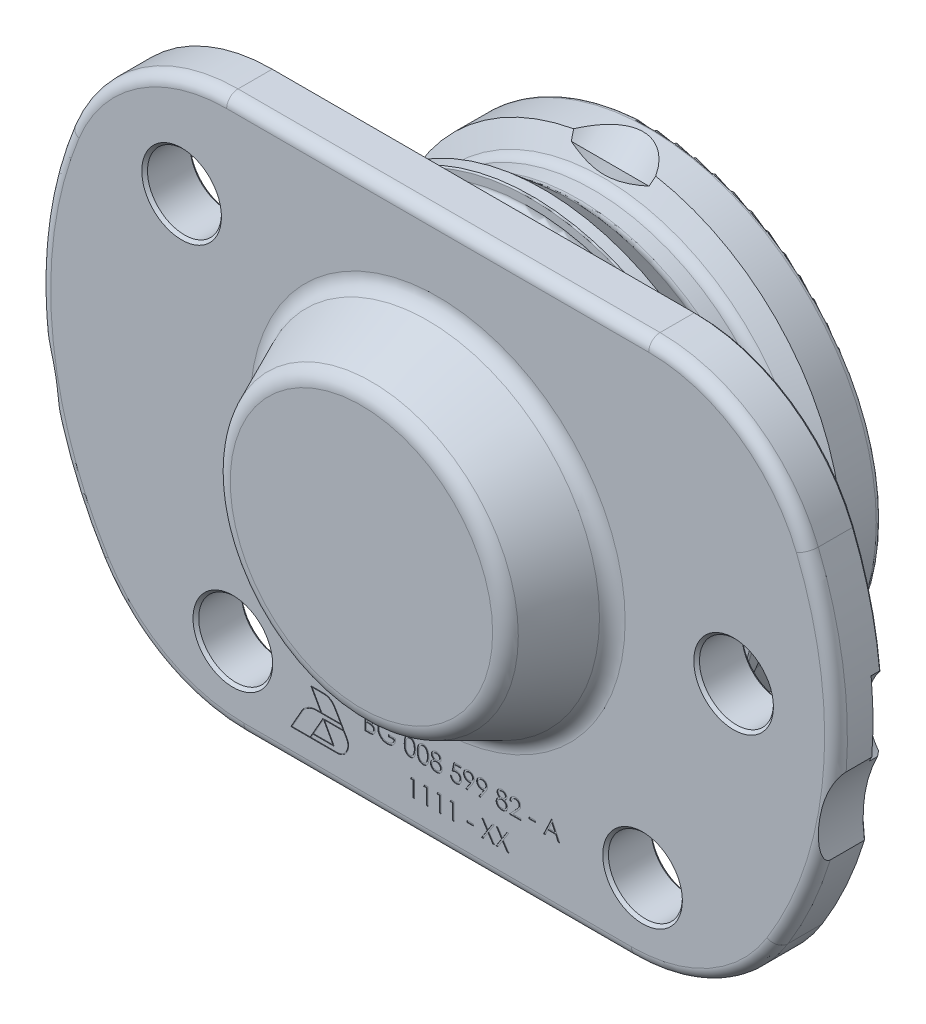
SolidWorks part; units mm, degrees
material "4140 H/T"
ref_plane "Front Plane" through (0, 0, 0) normal (0, 0, 1) x (1, 0, 0)
ref_plane "Top Plane" through (0, 0, 0) normal (0, 1, 0) x (1, 0, 0)
ref_plane "Right Plane" through (0, 0, 0) normal (1, 0, 0) x (0, 0, -1)
sketch "Sketch1" plane through (0, 0, 0) normal (0, 0, 1) x (1, 0, 0)
  line L0 (0, 0) -> (0, 80.5895) construction
  line L1 (0, 0) -> (-118.5076, 0) construction
  line L2 (0, 0) -> (36, -37.5233) construction
  line L3 (37.081, 45) -> (-37.081, 45)
  line L4 (-34.0441, -51) -> (34.0441, -51)
  circle A0 centre (52, 0) radius 6.5
  circle A1 centre (36, -37.5233) radius 6.5
  circle A2 centre (-36, -37.5233) radius 6.5
  circle A3 centre (-45, 26.0576) radius 6.5
  arc A4 (-37.081, 45) -> (-64.8917, 26.25) centre (-37.081, 15) ccw
  arc A5 (-64.8917, 26.25) -> (-59.5772, -36.75) centre (0, 0) ccw
  arc A6 (-59.5772, -36.75) -> (-34.0441, -51) centre (-34.0441, -21) ccw
  arc A7 (59.5772, -36.75) -> (34.0441, -51) centre (34.0441, -21) cw
  arc A8 (64.8917, 26.25) -> (59.5772, -36.75) centre (0, 0) cw
  arc A9 (37.081, 45) -> (64.8917, 26.25) centre (37.081, 15) cw
  circle A10 centre (0, 0) radius 52 construction
  point P26 (0, -51)
  point P32 (0, 45)
  dimension "D1" = 13
  dimension "D5" = 30
  dimension "D6" = 30
  dimension "D7" = 140
  dimension "D8" = 70
  dimension "D9" = 104
  dimension "D10" = 45
  dimension "D11" = 36
  dimension "D12" = 36
  dimension "D2" = 45
  dimension "D3" = 51
  dimension "D13" = 46.187
extrude "Extrude1" add sketch "Sketch1" along normal blind 8.5
sketch "Sketch2" plane through (0, 0, 0) normal (1, 0, 0) x (0, 0, -1)
  line L0 (0, 0) -> (34.8512, 0) construction
  line L1 (0, 39.975) -> (3.85, 39.975)
  line L2 (0, 26.25) -> (0, 45) construction
  line L3 (4.1, 39.725) -> (4.1, 38.35)
  line L4 (4.9, 37.55) -> (7, 37.55)
  line L5 (7.8, 38.35) -> (7.8, 39.725)
  line L6 (8.05, 39.975) -> (10.1, 39.975)
  line L7 (109.361, 150.8299) -> (109.361, 125.8299) construction
  line L8 (29.6, 38.975) -> (29.6, 0)
  line L9 (0, 39.975) -> (-8.5, 39.975)
  line L10 (-8.5, 45) -> (-8.5, 26.25) construction
  line L11 (-8.5, 39.975) -> (-8.5, 32.9437)
  line L12 (-8.5, 26.25) -> (-8.5, -36.75) construction
  line L13 (-10.274, 30.2057) -> (-20.126, 25.7943)
  line L14 (-21.9, 23.0563) -> (-21.9, 0)
  line L15 (29.6, 0) -> (-21.9, 0)
  line L16 (10.1, 39.975) -> (14.8755, 35.9679)
  line L17 (22.6, 39.975) -> (20.5937, 36.5)
  line L18 (18.8617, 35.5) -> (16.161, 35.5)
  line L19 (22.6, 39.975) -> (28.6, 39.975)
  line L20 (62.484, 84.927) -> (62.484, 164.927) construction
  line L21 (60.9185, 95.9953) -> (60.9185, 65.5229) construction
  line L22 (57.8623, 92.6695) -> (57.8623, 65.5229) construction
  line L23 (79.7053, 87.2761) -> (79.7053, 68.4893) construction
  line L24 (64.6938, 84.6693) -> (67.4146, 89.3819) construction
  line L25 (67.4146, 89.3819) -> (71.4823, 89.3819) construction
  line L26 (71.4823, 89.3819) -> (77.0985, 84.6693) construction
  line L27 (64.6938, 84.6693) -> (38.8957, 84.6693) construction
  line L28 (88.1305, 125.8299) -> (6.95, 125.8299) construction
  line L29 (74.2904, 87.0256) -> (85.5084, 101.1776) construction
  line L30 (109.361, 125.8299) -> (96.5029, 125.8299) construction
  line L31 (96.5029, 125.8299) -> (96.5029, 156.8299) construction
  line L32 (87.7036, 81.3976) -> (95.948, 81.3976) construction
  line L33 (109.361, 133.7274) -> (57.8623, 133.7274) construction
  line L34 (87.7036, 81.3976) -> (87.7036, 62.5034) construction
  arc A0 (-20.126, 25.7943) -> (-21.9, 23.0563) centre (-18.9, 23.0563) ccw
  arc A1 (-8.5, 32.9437) -> (-10.274, 30.2057) centre (-11.5, 32.9437) cw
  arc A2 (4.1, 38.35) -> (4.9, 37.55) centre (4.9, 38.35) ccw
  arc A3 (7, 37.55) -> (7.8, 38.35) centre (7, 38.35) ccw
  arc A4 (7.8, 39.725) -> (8.05, 39.975) centre (8.05, 39.725) cw
  arc A5 (3.85, 39.975) -> (4.1, 39.725) centre (3.85, 39.725) cw
  arc A6 (20.5937, 36.5) -> (18.8617, 35.5) centre (18.8617, 37.5) cw
  arc A7 (14.8755, 35.9679) -> (16.161, 35.5) centre (16.161, 37.5) ccw
  arc A8 (29.6, 38.975) -> (28.6, 39.975) centre (28.6, 38.975) ccw
  point P23 (-21.9, 25)
  point P26 (-8.5, 31)
  dimension "D4" = 3
  dimension "D12" = 0.8
  dimension "D13" = 0.25
  dimension "D29" = 2
  dimension "D10" = 1
  dimension "D2" = 50
  dimension "D3" = 62
  dimension "D5" = 79.95
  dimension "D6" = 29.6
  dimension "D7" = 75.1
  dimension "D8" = 3.7
  dimension "D9" = 21.8
  dimension "D11" = 2.425
  dimension "D14" = 51.5
  dimension "D15" = 80
  dimension "D16" = 6.8316
  dimension "D17" = 19.2363
  dimension "D18" = 60
  dimension "D19" = 40
  dimension "D20" = 21.8431
  dimension "D21" = 19.2363
  dimension "D22" = 7
  dimension "D23" = 19.5
  dimension "D24" = 60
  dimension "D25" = 40
  dimension "D26" = 71
  dimension "D27" = 3.0562
  dimension "D28" = 51.597
  dimension "D30" = 25
  dimension "D31" = 31
  dimension "D32" = 51.4987
revolve "Revolve1" add sketch "Sketch2" angle 360 about L0
fillet "Fillet5" radius 0.8 1 edges at (39.975, 0, 0)
sketch "Sketch3" plane through (0, 0, 0) normal (1, 0, 0) x (0, 0, -1)
  line L0 (0, 0) -> (47.3873, 0) construction
  line L1 (29.6, 32) -> (26.8929, 29.2929)
  line L3 (26.1858, 29) -> (-1.3282, 29)
  line L4 (-3.3282, 28.4641) -> (-12.4, 23.2265)
  line L5 (-14.4, 19.7624) -> (-14.4, 0)
  line L6 (29.6, 32) -> (29.6, 0)
  line L7 (-14.4, 0) -> (29.6, 0)
  line L9 (29.6, 38.975) -> (29.6, 0) construction
  arc A0 (-12.4, 23.2265) -> (-14.4, 19.7624) centre (-10.4, 19.7624) ccw
  arc A1 (-1.3282, 29) -> (-3.3282, 28.4641) centre (-1.3282, 25) ccw
  arc A2 (26.8929, 29.2929) -> (26.1858, 29) centre (26.1858, 30) cw
  point P13 (-14.4, 22.0718)
  point P16 (-2.4, 29)
  point P19 (26.6, 29)
  dimension "D7" = 4
  dimension "D8" = 1
  dimension "D1" = 64
  dimension "D2" = 58
  dimension "D3" = 45
  dimension "D4" = 32
  dimension "D5" = 44
  dimension "D6" = 30
  dimension "D9" = 3
revolve "Cut-Revolve1" cut sketch "Sketch3" angle 360 about L0
ref_plane "Plane3" through (0, 0, -20.6) normal (0, 0, -1) x (-1, 0, 0)
fillet "Fillet1" radius 2 8 edges at (53.8515, 39.8747, 8.5) (69.7522, -5.8842, 8.5) (48.6643, -47.1964, 8.5) (0, -51, 8.5) (-48.6643, -47.1964, 8.5) (-69.7522, -5.8842, 8.5) (-53.8515, 39.8747, 8.5) (0, 45, 8.5)
sketch "Sketch9" plane through (0, 0, 0) normal (1, 0, 0) x (0, 0, -1)
  line L0 (22.8839, -48.7703) -> (-1.0551, -20.241) construction
  line L1 (13.6, -37.7062) -> (15.5151, -36.0993) construction
  line L2 (15.5151, -36.0993) -> (12.3012, -32.2691)
  line L3 (13.6, -37.7062) -> (2.8578, -24.9042)
  line L4 (29.7, -38.975) -> (29.7, 38.975) construction
  line L5 (0, 0) -> (43.186, 0) construction
  line L6 (2.8578, -24.9042) -> (3.6239, -24.2615)
  line L7 (7.6, -29) -> (7.6, -24.6889) construction
  line L8 (12.3012, -32.2691) -> (10.5728, -32.5428)
  line L9 (10.5728, -32.5428) -> (3.6239, -24.2615)
  line L10 (29.6, -32) -> (29.6, 32) construction
  line L11 (15.5151, -36.0993) -> (20.5701, -42.1235)
  line L12 (20.5701, -42.1235) -> (18.6549, -43.7305)
  line L13 (13.6, -37.7062) -> (18.6549, -43.7305)
  dimension "D1" = 5
  dimension "D2" = 14.1849
  dimension "D3" = 37.7062
  dimension "D4" = 29
  dimension "D5" = 16
  dimension "D6" = 5
  dimension "D7" = 2
  dimension "D8" = 59
  dimension "D9" = 16.7118
  dimension "D10" = 50
  dimension "D11" = 7.8641
  dimension "D12" = 22
revolve "Cut-Revolve3" cut sketch "Sketch9" angle 360 about L3
ref_axis "Axis1" through (0, 0, -26.1858) along (0, 0, 1)
pattern_circular "CirPattern1" count 3 over 360 about axis through (0, 0, -26.1858) along (0, 0, 1) of "Cut-Revolve3"
sketch "Sketch11" plane through (0, 0, 0) normal (0, 0, -1) x (-1, 0, 0)
  line L0 (0, 0) -> (0, 55.2729) construction
  circle A0 centre (77, 0) radius 10
  circle A1 centre (-77, 0) radius 10
  dimension "D1" = 154
  dimension "D2" = 20
extrude "Cut-Extrude1" cut sketch "Sketch11" against normal blind 2
sketch "Sketch13" plane through (0, 0, 0) normal (0, 0, -1) x (-1, 0, 0)
  line L0 (0, 0) -> (0, -62.4368) construction
  circle A0 centre (-90, -17) radius 23.25
  circle A1 centre (90, -17) radius 23.25
  dimension "D1" = 46.5
  dimension "D2" = 180
  dimension "D3" = 17
extrude "Cut-Extrude2" cut sketch "Sketch13" against normal through all
chamfer "Chamfer3" distance 0.5 angle 45 19 edges at (-29.5, -37.5233, 8.5) (58.5, 0, 8.5) (42.5, -37.5233, 8.5) (-38.5, 26.0576, 8.5) (-29.5, -37.5233, 0) (58.5, 0, 0) (-48.6643, -47.1964, 0) (0, -51, 0) (48.6643, -47.1964, 0) (63.8137, -28.7718, 0) (67.9794, 16.6972, 0) (53.8515, 39.8747, 0) (0, 45, 0) (-53.8515, 39.8747, 0) (42.5, -37.5233, 0) (-38.5, 26.0576, 0) (-63.8137, -28.7718, 0) (67.0671, -13.1733, 0) (-67.0671, -13.1733, 0)
sketch "Sketch8" plane through (0, 0, 8.5) normal (0, 0, 1) x (1, 0, 0)
  line L0 (-15.5317, -39.5131) -> (22.8523, -39.5131) construction
  text T0 " BG 008 599 82 - A\r\n1111 - XX" font "Century Gothic" height 3
  point P3 (-15.5317, -39.5131)
  point P8 (-13.0536, -39.7517)
  point P9 (22.8523, -39.7098)
  line B0 (-17.7287, -45.401) -> (-22.3045, -45.401)
  line B1 (-18.4065, -44.4682) -> (-21.7741, -44.4682)
  line B2 (-22.2249, -45.261) -> (-21.8537, -44.6082)
  line B3 (-20.5433, -40.5791) -> (-21.3414, -40.5791)
  line B4 (-22.3045, -37.4096) -> (-20.5433, -40.5791)
  line B5 (-18.4065, -44.4682) -> (-20.0647, -41.4621)
  line B6 (-16.3835, -41.4621) -> (-15.9652, -42.185)
  line B7 (-20.0589, -37.4096) -> (-22.3045, -37.4096)
  line B8 (-16.8651, -40.5791) -> (-16.3835, -41.4621)
  line B9 (-16.8651, -40.5791) -> (-18.0744, -38.5399)
  line B10 (-22.3045, -45.401) -> (-25.8009, -45.401)
  line B11 (-23.8352, -41.9442) -> (-25.8009, -45.401)
  line B12 (-16.5875, -41.3216) -> (-16.9448, -40.7191)
  line B13 (-20.0589, -37.5496) -> (-22.0666, -37.5496)
  line B14 (-22.0666, -37.5496) -> (-20.3832, -40.5791)
  line B15 (-21.3414, -40.7191) -> (-16.9448, -40.7191)
  line B16 (-23.7154, -42.0166) -> (-25.5603, -45.261)
  line B17 (-22.386, -45.261) -> (-25.5603, -45.261)
  line B18 (-20.0166, -45.401) -> (-20.0166, -34.6413) construction
  line B19 (-20.1459, -41.3216) -> (-16.5875, -41.3216)
  line B20 (-22.386, -45.261) -> (-20.1459, -41.3216)
  line B21 (-16.5453, -41.4621) -> (-16.0849, -42.2578)
  line B22 (-17.7287, -45.261) -> (-22.2249, -45.261)
  line B23 (-20.3832, -40.5791) -> (-17.0278, -40.5791)
  line B24 (-17.0278, -40.5791) -> (-18.1948, -38.6113)
  line B25 (-18.1694, -44.6082) -> (-21.8537, -44.6082)
  line B26 (-18.1694, -44.6082) -> (-19.9048, -41.4621)
  line B27 (-19.9048, -41.4621) -> (-16.5453, -41.4621)
  line B28 (-21.7741, -44.4682) -> (-20.0647, -41.4621)
  arc B29 (-18.0744, -38.5399) -> (-20.0589, -37.4096) centre (-20.0589, -39.7168) ccw
  arc B30 (-17.7287, -45.401) -> (-15.9652, -42.185) centre (-17.7287, -43.3095) ccw
  arc B31 (-21.3414, -40.5791) -> (-23.8352, -41.9442) centre (-21.3414, -43.5397) ccw
  arc B32 (-18.1948, -38.6113) -> (-20.0589, -37.5496) centre (-20.0589, -39.7168) ccw
  arc B33 (-21.3414, -40.7191) -> (-23.7154, -42.0166) centre (-21.3414, -43.5397) ccw
  arc B34 (-17.7287, -45.261) -> (-16.0849, -42.2578) centre (-17.7287, -43.3095) ccw
sketch_block_instance "SKETCH LOGO-1"
sketch_block "SKETCH LOGO" parameters "D1"=29.059, "D2"=11.4163, "D3"=29.624, "D4"=6.8884
extrude "ENGRAVE PN" cut sketch "Sketch8" against normal blind 0.1
sketch "Sketch12" plane through (0, 0, 0) normal (1, 0, 0) x (0, 0, -1)
  line L0 (0, 0) -> (44.0485, 0) construction
  line L1 (27.1851, 53.7022) -> (-3.7778, 22.7394) construction
  line L2 (25.0491, 51.5662) -> (32.1202, 44.4952)
  line L3 (32.1202, 44.4952) -> (23.7109, 36.0859)
  line L4 (23.7109, 36.0859) -> (12.3911, 38.9083)
  line L5 (27.6, 39.975) -> (27.6, 37.4112) construction
  line L6 (22.6, 39.975) -> (28.6, 39.975) construction
  line L7 (29.6, 38.975) -> (29.6, 0) construction
  line L8 (13.4579, 39.975) -> (18.1729, 35.26) construction
  line L9 (25.0491, 51.5662) -> (12.3911, 38.9083)
  dimension "D1" = 59
  dimension "D2" = 2
  dimension "D3" = 20
  dimension "D4" = 45
  dimension "D5" = 16.3925
  dimension "D6" = 5.5
revolve "Cut-Revolve4" cut sketch "Sketch12" angle 360 about L1
